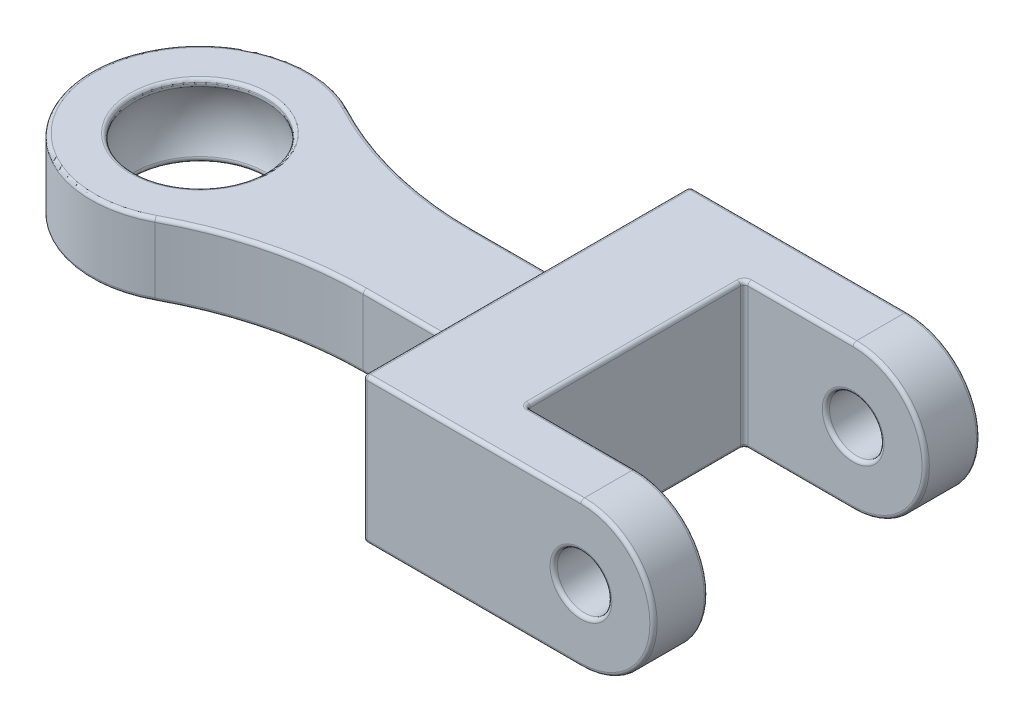
SolidWorks part; units mm, degrees
ref_plane "Front Plane" through (0, 0, 0) normal (0, 0, 1) x (1, 0, 0)
ref_plane "Top Plane" through (0, 0, 0) normal (0, 1, 0) x (1, 0, 0)
ref_plane "Right Plane" through (0, 0, 0) normal (1, 0, 0) x (0, 0, -1)
sketch "Sketch1" plane through (0, 0, 0) normal (0, 0, 1) x (1, 0, 0)
  line L0 (0, 2) -> (-6, 2)
  line L1 (-6, 2) -> (-6, -2)
  line L2 (-6, -2) -> (0, -2)
  circle A0 centre (0, 0) radius 0.75
  arc A1 (0, -2) -> (0, 2) centre (0, 0) ccw
  point P6 (-4.8934, -2)
  dimension "D1" = 4
  dimension "D2" = 1.5
  dimension "D3" = 6
extrude "Boss-Extrude1" add sketch "Sketch1" along normal mid plane 9
sketch "Sketch2" plane through (0, 0, 0) normal (0, 1, 0) x (1, 0, 0)
  line L0 (2, -4.5) -> (2, 4.5) construction
  line L1 (-3, -3) -> (3, -3)
  line L2 (-3, -3) -> (-3, 3)
  line L3 (-3, 3) -> (3, 3)
  line L4 (3, -3) -> (3, 3)
  line L5 (-3, -3) -> (3, 3) construction
  line L6 (-3, 3) -> (3, -3) construction
  point P0 (0, 0)
  dimension "D1" = 6
  dimension "D2" = 5
extrude "Cut-Extrude1" cut sketch "Sketch2" against normal through all both and the other way through all
sketch "Sketch3" plane through (0, 0, 0) normal (0, 1, 0) x (1, 0, 0)
  circle A0 centre (-15, 0) radius 1.375
  circle A1 centre (-15, 0) radius 2 construction
  circle A2 centre (-15, 0) radius 3
  dimension "D2" = 6
  dimension "D3" = 4
  dimension "D4" = 2.75
  dimension "D1" = 15
sketch "Sketch4" plane through (0, 0, 0) normal (0, 1, 0) x (1, 0, 0)
  line L0 (-6, 1.5) -> (-6, -1.5)
  line L1 (-6, -4.5) -> (-6, 4.5) construction
  line L2 (-6, 1.5) -> (-9, 1.5)
  line L3 (0, 0) -> (-1.9007, 0) construction
  line L4 (-6, -1.5) -> (-9, -1.5)
  circle A0 centre (-15, 0) radius 3 construction
  arc A1 (-13.5882, 2.6471) -> (-13.5882, -2.6471) centre (-15, 0) ccw
  arc A2 (-9, 1.5) -> (-13.5882, 2.6471) centre (-9, 11.25) cw
  arc A3 (-9, -1.5) -> (-13.5882, -2.6471) centre (-9, -11.25) ccw
  circle A4 centre (-15, 0) radius 1.375 construction
  circle A5 centre (-15, 0) radius 1.375
  point P7 (-6, 0)
  point P8 (-6, 0)
  dimension "D1" = 3
  dimension "D2" = 3
extrude "Boss-Extrude2" add sketch "Sketch4" along normal mid plane 2
sketch "Sketch5" plane through (0, 0, 0) normal (0, 1, 0) x (1, 0, 0)
  line L0 (-15, 2) -> (-15, -2)
  circle A0 centre (-15, 0) radius 2 construction
  arc A1 (-15, 2) -> (-15, -2) centre (-15, 0) ccw
revolve "Revolve1" add sketch "Sketch5" angle 360 about L0
combine bodies "Combine1" operation type subtract main body 103 bodies to subtract 104
fillet "Fillet1" radius 0.25 4 edges at (-6, 0, -1.5) (-6, -1, 0) (-6, 0, 1.5) (-6, 1, 0)
chamfer "Chamfer1" distance 0.15 angle 45 2 edges at (-15, -1, -1.7321) (-15, 1, -1.7321) first distance on face at (-15, -1, -1.7321)
fillet "Fillet2" radius 0.1 42 edges at (-6.0732, -1.0732, -1.5732) (-6.0732, 1.0732, -1.5732) (-6.0732, -1.0732, 1.5732) (-6.0732, 1.0732, 1.5732) (-7.625, -1, -1.5) (-11.3647, -1, -1.7911) (-18, -1, 0) (-11.3647, -1, 1.7911) (-7.625, -1, 1.5) (-7.625, 1, -1.5) (-11.3647, 1, -1.7911) (-18, 1, 0) (-7.625, 1, 1.5) (-1.5, 2, -3) (-3, 2, 0) (-1.5, 2, 3) (-1.5, -2, -3) (-3, -2, 0) (-1.5, -2, 3) (-3, 0, -3) (-3, 0, 3) (-0.75, 0, -3) (2, 0, -3) (0.75, 0, 3) (2, 0, 3) (0.75, 0, -4.5) (0.75, 0, 4.5) (2, 0, -4.5) (-3, 2, -4.5) (-6, 0, -4.5) (-3, -2, -4.5) (2, 0, 4.5) (-3, 2, 4.5) (-6, 0, 4.5) (-3, -2, 4.5) (-6, -2, 0) (-6, 2, 0) (-15, 0.8618, -1.8048) (-15, -0.9027, 1.7847) (-15, -1, -1.8821) (-15, 1, -1.8419) (-11.3647, 1, 1.7911)
